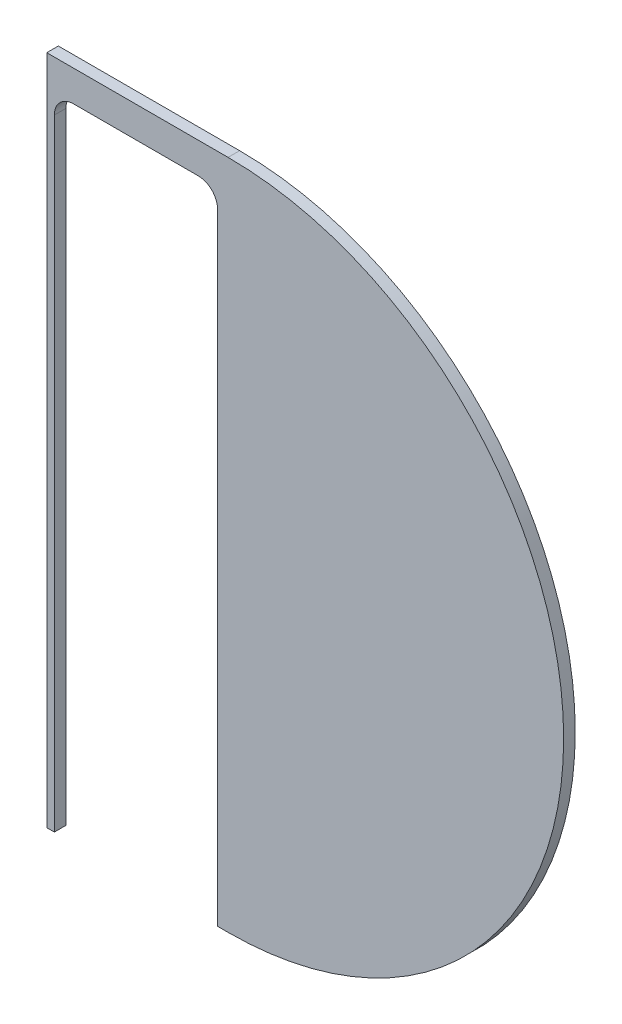
SolidWorks part; units mm, degrees
ref_plane "Front Plane" through (0, 0, 0) normal (0, 0, 1) x (1, 0, 0)
ref_plane "Top Plane" through (0, 0, 0) normal (0, 1, 0) x (1, 0, 0)
ref_plane "Right Plane" through (0, 0, 0) normal (1, 0, 0) x (0, 0, -1)
sketch "Sketch1" plane through (0, 0, 0) normal (0, 0, 1) x (1, 0, 0)
  line L1 (0, 0) -> (470, 0)
  line L2 (0, 0) -> (0, 1740)
  line L3 (0, 1740) -> (470, 1740)
  line L4 (470, 0) -> (470, 1740) construction
  arc A0 (470, 1740) -> (470, 0) centre (470, 870) cw
  dimension "D1" = 470
  dimension "D2" = 1740
extrude "Boss-Extrude1" add sketch "Sketch1" along normal blind 30
extrude "Cut-Extrude1" cut sketch "Sketch2" against normal through all
sketch "Sketch2" plane through (-149.8935, 64.2521, -2) normal (0, 0, -1) x (-1, 0, 0)
  line L1 (-592.7736, -114.2521) -> (-169.5721, -114.2521)
  line L2 (-592.7736, -114.2521) -> (-592.7736, 1545.5946)
  line L3 (-542.7736, 1595.5946) -> (-219.5721, 1595.5946)
  line L4 (-169.5721, -114.2521) -> (-169.5721, 1545.5946)
  arc A0 (-219.5721, 1595.5946) -> (-169.5721, 1545.5946) centre (-219.5721, 1545.5946) cw
  arc A1 (-592.7736, 1545.5946) -> (-542.7736, 1595.5946) centre (-542.7736, 1545.5946) cw
